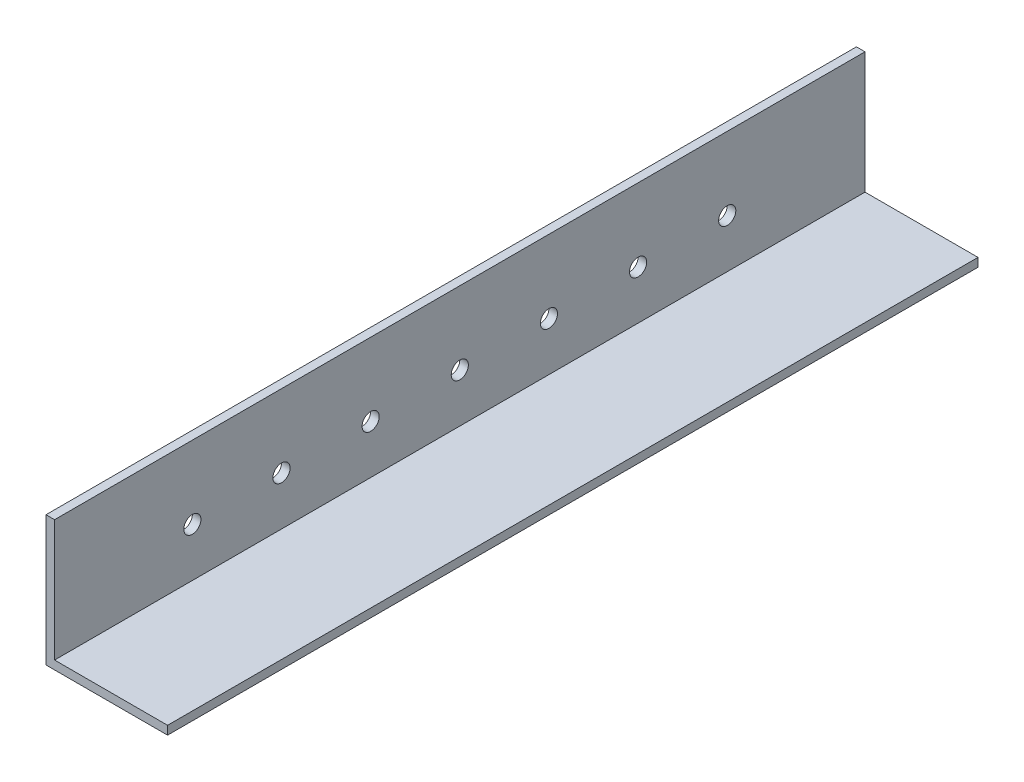
SolidWorks part; units mm, degrees
ref_plane "Alzado" through (0, 0, 0) normal (0, 0, 1) x (1, 0, 0)
ref_plane "Planta" through (0, 0, 0) normal (0, 1, 0) x (1, 0, 0)
ref_plane "Vista lateral" through (0, 0, 0) normal (1, 0, 0) x (0, 0, -1)
sketch "Croquis1" plane through (0, 0, 0) normal (0, 0, 1) x (1, 0, 0)
  line L0 (-19.325, 0) -> (0, 0) construction
  line L1 (22.5, -25.675) -> (-22.5, -25.675)
  line L2 (22.5, -25.675) -> (22.5, -22.5)
  line L3 (22.5, -22.5) -> (-22.5, -22.5)
  line L4 (-22.5, -25.675) -> (-22.5, -22.5)
  line L5 (-22.5, -22.5) -> (-19.325, -22.5)
  line L6 (-22.5, -22.5) -> (-22.5, 22.5)
  line L7 (-22.5, 22.5) -> (-19.325, 22.5)
  line L8 (-19.325, -22.5) -> (-19.325, 22.5)
  line L9 (0, 0) -> (0, -22.5) construction
  dimension "D1" = 3.175
  dimension "D2" = 3.175
  dimension "D3" = 45
  dimension "D4" = 45
extrude "Saliente-Extruir1" add sketch "Croquis1" along normal mid plane 300 contours L3 L8 L7 L6 | L4 L1 L2 L3 region at (0, -24.0875, 0) region at (-20.9125, 0, 0)
sketch "Croquis2" plane through (0, 0, 0) normal (1, 0, 0) x (0, 0, -1)
  line L0 (-185.7724, -4.5) -> (180.2818, -4.5) construction
  line L1 (0, 9.483) -> (0, -16.9346) construction
  line L2 (-152.7724, -4.5) -> (213.2818, -4.5) construction
  line L3 (-119.7724, -4.5) -> (246.2818, -4.5) construction
  line L4 (-86.7724, -4.5) -> (279.2818, -4.5) construction
  line L5 (-150, -22.5) -> (150, -22.5) construction
  line L6 (-150, -22.5) -> (150, -22.5) construction
  line L17 (-185.7724, -0.787) -> (180.2818, -0.787) construction
  line L18 (-152.7724, -0.787) -> (213.2818, -0.787) construction
  line L19 (-119.7724, -0.787) -> (246.2818, -0.787) construction
  line L20 (-218.7724, -0.787) -> (147.2818, -0.787) construction
  line L21 (-218.7724, 2.926) -> (147.2818, 2.926) construction
  line L22 (-185.7724, 2.926) -> (180.2818, 2.926) construction
  line L23 (-152.7724, 2.926) -> (213.2818, 2.926) construction
  line L24 (-251.7724, 2.926) -> (114.2818, 2.926) construction
  line L25 (-251.7724, 6.6391) -> (114.2818, 6.6391) construction
  line L26 (-218.7724, 6.6391) -> (147.2818, 6.6391) construction
  line L27 (-185.7724, 6.6391) -> (180.2818, 6.6391) construction
  line L28 (-284.7724, 6.6391) -> (81.2818, 6.6391) construction
  circle A0 centre (0, -4.5) radius 3.175
  circle A1 centre (33, -4.5) radius 3.175
  circle A2 centre (66, -4.5) radius 3.175
  circle A3 centre (99, -4.5) radius 3.175
  circle A16 centre (-66, 2.926) radius 3.175 [skipped]
  circle A17 centre (-33, 2.926) radius 3.175 [skipped]
  circle A18 centre (-33, -0.787) radius 3.175 [skipped]
  circle A19 centre (-33, 6.6391) radius 3.175 [skipped]
  circle A20 centre (-66, 6.6391) radius 3.175 [skipped]
  circle A21 centre (0, 6.6391) radius 3.175 [skipped]
  circle A22 centre (0, 2.926) radius 3.175 [skipped]
  circle A23 centre (0, -0.787) radius 3.175 [skipped]
  circle A24 centre (33, 2.926) radius 3.175 [skipped]
  circle A25 centre (33, -0.787) radius 3.175 [skipped]
  circle A26 centre (-99, 6.6391) radius 3.175 [skipped]
  circle A27 centre (66, -0.787) radius 3.175 [skipped]
  circle A28 centre (-99, -4.5) radius 3.175
  circle A29 centre (-66, -4.5) radius 3.175
  circle A30 centre (-33, -4.5) radius 3.175
  dimension "D2" = 6.35
  dimension "D1" = 4.5
  dimension "D5" = 33
  dimension "D6" = 18
  dimension "D7" = 18
  dimension "D3" = 4
  dimension "D4" = 4
extrude "Cortar-Extruir1" cut sketch "Croquis2" against normal blind 50
